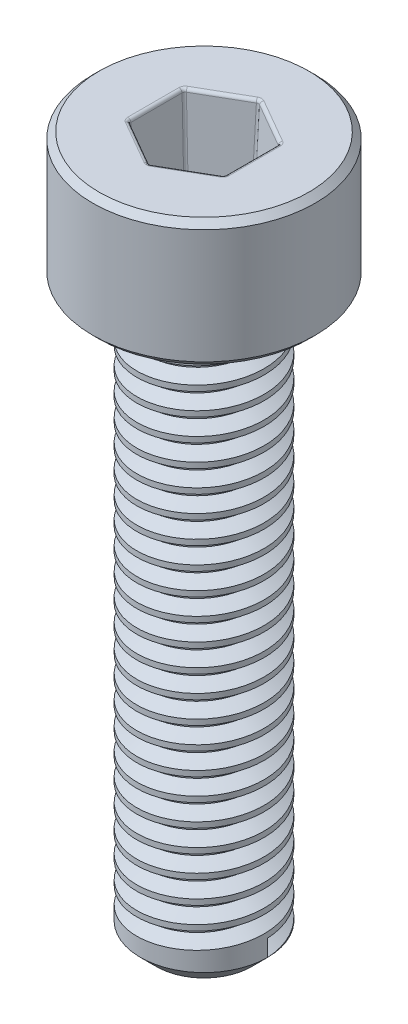
SolidWorks part; units mm, degrees
ref_plane "Спереди" through (0, 0, 0) normal (0, 0, 1) x (1, 0, 0)
ref_plane "Сверху" through (0, 0, 0) normal (0, 1, 0) x (1, 0, 0)
ref_plane "Справа" through (0, 0, 0) normal (1, 0, 0) x (0, 0, -1)
sketch "Эскиз1" plane through (0, 0, 0) normal (0, 1, 0) x (1, 0, 0)
  circle A0 centre (0, 0) radius 3.5
extrude "Бобышка-Вытянуть1" add sketch "Эскиз1" along normal blind 4
sketch "Эскиз2" plane through (0, 4, 0) normal (0, 1, 0) x (1, 0, 0)
  line L1 (0, 1.7321) -> (-1.5, 0.866)
  line L2 (-1.5, 0.866) -> (-1.5, -0.866)
  line L3 (-1.5, -0.866) -> (0, -1.7321)
  line L4 (0, -1.7321) -> (1.5, -0.866)
  line L5 (1.5, -0.866) -> (1.5, 0.866)
  line L6 (1.5, 0.866) -> (0, 1.7321)
  circle A0 centre (0, 0) radius 1.5 construction
extrude "Вырез-Вытянуть1" cut sketch "Эскиз2" against normal blind 3 draft 3
fillet "Скругление1" radius 0.1 18 edges at (0.75, 4, -1.299) (-0.75, 4, -1.299) (1.5, 4, 0) (-1.5, 4, 0) (0.75, 4, 1.299) (1.3428, 1, 0) (0.6714, 1, 1.1629) (-0.6714, 1, 1.1629) (-1.3428, 1, 0) (-0.6714, 1, -1.1629) (0.6714, 1, -1.1629) (-0.75, 4, 1.299) (-1.4214, 2.5, 0.8206) (0, 2.5, 1.6413) (1.4214, 2.5, 0.8206) (1.4214, 2.5, -0.8206) (0, 2.5, -1.6413) (-1.4214, 2.5, -0.8206)
chamfer "Фаска1" distance 0.2 angle 45 2 edges at (0, 0, 3.5) (0, 4, 3.5)
sketch "Эскиз3" plane through (0, 0, 0) normal (0, -1, 0) x (1, 0, 0)
  circle A0 centre (0, 0) radius 2
extrude "Бобышка-Вытянуть2" add sketch "Эскиз3" along normal blind 18
chamfer "Фаска2" distance 0.5 angle 45 1 edges at (0, -18, -2)
thread "Резьба1" pitch 0.7 method cut profile "Профиль резьбы1" start angle 0, offset 0, length 0, pitch 0.7, diameter 4
ref_plane "Плоскость1" through (2, -17.5, 0) normal (0, 0, -1) x (-1, 0, 0)
sketch "Профиль резьбы1" plane through (2, -17.5, 0) normal (0, 0, -1) x (-1, 0, 0)
  line L0 (0, 0) -> (0, 0.7) construction
  line L1 (0, 0) -> (0.3789, 0.2187)
  line L2 (0.3789, 0.2187) -> (0.3789, 0.3062)
  line L3 (0.3789, 0.3062) -> (0, 0.525)
  line L4 (0.3789, 0.2625) -> (0, 0.2625) construction
  line L11 (0, 0) -> (0, 0.525)
  point P2 (0, 0)
  dimension "Pitch" = 0.7
  dimension "Profile_Angle" = 60
  dimension "Profile_Land" = 0.0875
  dimension "Profile_Height" = 0.3789
sketch "Эскиз4" plane through (0, 4, 0) normal (0, 1, 0) x (1, 0, 0)
  circle A0 centre (0, 0) radius 3.6785 construction
  circle A1 centre (0, 3.6785) radius 0.2185
  circle A2 centre (0.5754, 3.6332) radius 0.2185
  circle A3 centre (1.1367, 3.4985) radius 0.2185
  circle A4 centre (1.67, 3.2776) radius 0.2185
  circle A5 centre (2.1622, 2.976) radius 0.2185
  circle A6 centre (2.6011, 2.6011) radius 0.2185
  circle A7 centre (2.976, 2.1622) radius 0.2185
  circle A8 centre (3.2776, 1.67) radius 0.2185
  circle A9 centre (3.4985, 1.1367) radius 0.2185
  circle A10 centre (3.6332, 0.5754) radius 0.2185
  circle A11 centre (3.6785, 0) radius 0.2185
  circle A12 centre (3.6332, -0.5754) radius 0.2185
  circle A13 centre (3.4985, -1.1367) radius 0.2185
  circle A14 centre (3.2776, -1.67) radius 0.2185
  circle A15 centre (2.976, -2.1622) radius 0.2185
  circle A16 centre (2.6011, -2.6011) radius 0.2185
  circle A17 centre (2.1622, -2.976) radius 0.2185
  circle A18 centre (1.67, -3.2776) radius 0.2185
  circle A19 centre (1.1367, -3.4985) radius 0.2185
  circle A20 centre (0.5754, -3.6332) radius 0.2185
  circle A21 centre (0, -3.6785) radius 0.2185
  circle A22 centre (-0.5754, -3.6332) radius 0.2185
  circle A23 centre (-1.1367, -3.4985) radius 0.2185
  circle A24 centre (-1.67, -3.2776) radius 0.2185
  circle A25 centre (-2.1622, -2.976) radius 0.2185
  circle A26 centre (-2.6011, -2.6011) radius 0.2185
  circle A27 centre (-2.976, -2.1622) radius 0.2185
  circle A28 centre (-3.2776, -1.67) radius 0.2185
  circle A29 centre (-3.4985, -1.1367) radius 0.2185
  circle A30 centre (-3.6332, -0.5754) radius 0.2185
  circle A31 centre (-3.6785, 0) radius 0.2185
  circle A32 centre (-3.6332, 0.5754) radius 0.2185
  circle A33 centre (-3.4985, 1.1367) radius 0.2185
  circle A34 centre (-3.2776, 1.67) radius 0.2185
  circle A35 centre (-2.976, 2.1622) radius 0.2185
  circle A36 centre (-2.6011, 2.6011) radius 0.2185
  circle A37 centre (-2.1622, 2.976) radius 0.2185
  circle A38 centre (-1.67, 3.2776) radius 0.2185
  circle A39 centre (-1.1367, 3.4985) radius 0.2185
  circle A40 centre (-0.5754, 3.6332) radius 0.2185
  point P85 (0, 0)
  dimension "D1" = 40
extrude "Вырез-Вытянуть2" [suppressed] cut sketch "Эскиз4" against normal blind 3 from offset 0.15 offset against normal yes
